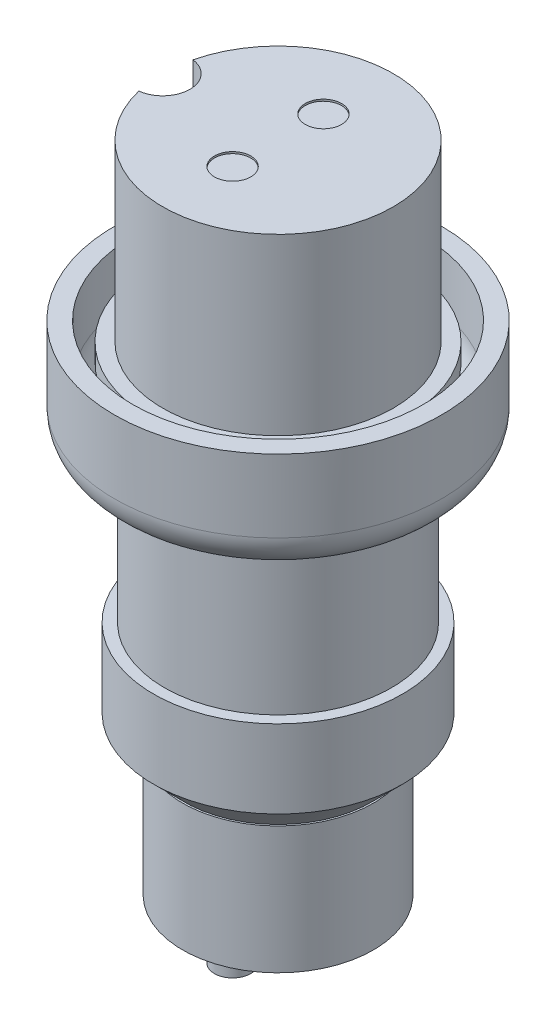
SolidWorks part; units mm, degrees
ref_plane "前视基准面" through (0, 0, 0) normal (0, 0, 1) x (1, 0, 0)
ref_plane "上视基准面" through (0, 0, 0) normal (0, 1, 0) x (1, 0, 0)
ref_plane "右视基准面" through (0, 0, 0) normal (1, 0, 0) x (0, 0, -1)
sketch "草图1" plane through (0, 0, 0) normal (0, 1, 0) x (1, 0, 0)
  circle A0 centre (0, 0) radius 6.35
  dimension "D1" = 12.7
extrude "凸台-拉伸1" add sketch "草图1" along normal blind 9.6
sketch "草图2" plane through (0, 0, 0) normal (0, -1, 0) x (-1, 0, 0)
  circle A0 centre (0, 0) radius 7.125
  dimension "D1" = 14.25
extrude "凸台-拉伸2" add sketch "草图2" along normal blind 1
sketch "草图3" plane through (0, -1, 0) normal (0, -1, 0) x (1, 0, 0)
  circle A0 centre (0, 0) radius 6.25
  dimension "D1" = 12.5
extrude "凸台-拉伸3" add sketch "草图3" along normal blind 12.38
sketch "草图4" plane through (0, -13.38, 0) normal (0, -1, 0) x (1, 0, 0)
  circle A0 centre (0, 0) radius 6.85
  dimension "D1" = 13.7
extrude "凸台-拉伸4" add sketch "草图4" along normal blind 6
chamfer "倒角1" distance 1.7 angle 45 1 edges at (0, -19.38, -6.85)
sketch "草图5" plane through (0, -19.38, 0) normal (0, -1, 0) x (1, 0, 0)
  circle A0 centre (0, 0) radius 5.25
  dimension "D1" = 10.5
extrude "凸台-拉伸5" add sketch "草图5" along normal blind 7
ref_plane "基准面1" through (0, -5, 0) normal (0, -1, 0) x (-1, 0, 0)
sketch "草图6" plane through (0, -5, 0) normal (0, -1, 0) x (-1, 0, 0)
  circle A0 centre (0, 0) radius 9
  dimension "D1" = 18
extrude "凸台-拉伸6" add sketch "草图6" against normal blind 1
sketch "草图7" plane through (0, -4, 0) normal (0, 1, 0) x (1, 0, 0)
  circle A0 centre (0, 0) radius 9 construction
  circle A1 centre (0, 0) radius 9
  circle A2 centre (0, 0) radius 8
  dimension "D1" = 1
extrude "凸台-拉伸7" add sketch "草图7" along normal blind 5
fillet "圆角1" radius 2 2 edges at (0, -4, 8) (0, -5, -9)
sketch "草图8" plane through (0, -26.38, 0) normal (0, -1, 0) x (1, 0, 0)
  line L0 (0, 0) -> (-1.8274, 0) construction
  circle A0 centre (0, -2.5) radius 1
  circle A1 centre (0, 2.5) radius 1
  dimension "D1" = 2
  dimension "D2" = 5
extrude "凸台-拉伸8" add sketch "草图8" along normal blind 2
sketch "草图9" plane through (0, 9.6, 0) normal (0, 1, 0) x (1, 0, 0)
  circle A0 centre (-6.35, 0) radius 1.5
  circle A1 centre (0, 0) radius 6.35 construction
  circle A2 centre (0, 0) radius 6.35 construction
  dimension "D1" = 3
extrude "切除-拉伸1" cut sketch "草图9" against normal up to surface (9.6 mm away) up to face at (0, 0, -6.35)
sketch "草图10" plane through (0, 9.6, 0) normal (0, 1, 0) x (1, 0, 0)
  circle A0 centre (0, -2.5) radius 1 construction
  circle A1 centre (0, 2.5) radius 1 construction
  circle A2 centre (0, -2.5) radius 1
  circle A3 centre (0, 2.5) radius 1
extrude "切除-拉伸2" cut sketch "草图10" against normal blind 0.1
sketch "草图11" plane through (0, -28.38, 0) normal (0, -1, 0) x (1, 0, 0)
  point P0 (0, -2.5)
  point P1 (0, 2.5)
other "连接点1" parameters "直径"=4.9, "端头长度"=2.25
ref_axis "基准轴1" through (0, -38.38, -2.5) along (0, 1, 0)
other "连接点2" parameters "直径"=4.9, "端头长度"=7.35
ref_axis "基准轴2" through (0, -38.38, 2.5) along (0, 1, 0)
